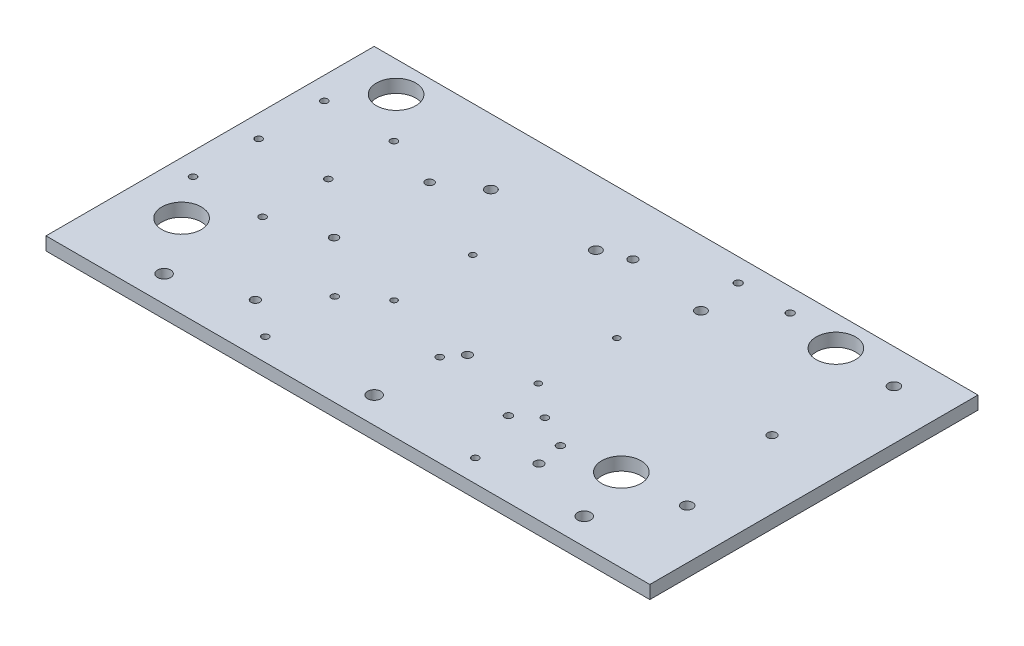
SolidWorks part; units mm, degrees
ref_plane "Front Plane" through (0, 0, 0) normal (0, 0, 1) x (1, 0, 0)
ref_plane "Top Plane" through (0, 0, 0) normal (0, 1, 0) x (1, 0, 0)
ref_plane "Right Plane" through (0, 0, 0) normal (1, 0, 0) x (0, 0, -1)
sketch "Sketch1" plane through (0, 0, 0) normal (0, 1, 0) x (1, 0, 0)
  line L1 (0, 0) -> (292.1, 0)
  line L2 (0, 0) -> (0, 158.75)
  line L3 (0, 158.75) -> (292.1, 158.75)
  line L4 (292.1, 0) -> (292.1, 158.75)
  dimension "D1" = 292.1
  dimension "D2" = 158.75
extrude "Boss-Extrude1" add sketch "Sketch1" along normal blind 6.35
sketch "Sketch2" plane through (0, 6.35, 0) normal (0, 1, 0) x (1, 0, 0)
  line L0 (0, 25.4) -> (292.1, 25.4) construction
  line L1 (0, 12.7) -> (292.1, 12.7) construction
  line L2 (146.05, 0) -> (146.05, 158.75) construction
  line L4 (0, 158.75) -> (0, 0)
  line L5 (0, 0) -> (292.1, 0)
  line L6 (292.1, 0) -> (292.1, 158.75)
  line L7 (292.1, 158.75) -> (0, 158.75)
  line L8 (0, 158.75) -> (0, 0) construction
  line L9 (0, 0) -> (292.1, 0) construction
  line L10 (292.1, 0) -> (292.1, 158.75) construction
  line L11 (292.1, 158.75) -> (0, 158.75) construction
  circle A0 centre (146.05, 12.7) radius 3.175
  circle A1 centre (247.65, 12.7) radius 3.175
  circle A2 centre (44.45, 12.7) radius 3.175
  dimension "D6" = 6.35
  dimension "D7" = 6.35
  dimension "D8" = 6.35
  dimension "D2" = 25.4
  dimension "D3" = 12.7
  dimension "D4" = 101.6
  dimension "D5" = 101.6
extrude "Cut-Extrude2" cut sketch "Sketch2" against normal blind 6.35
sketch "Sketch5" [suppressed] plane through (0, 6.35, 0) normal (0, 1, 0) x (1, 0, 0)
  line L0 (0, 0) -> (292.1, 0) construction
  line L1 (279.4, 31.75) -> (143.9, 31.75) construction
  line L2 (279.4, 31.75) -> (279.4, 75.25) construction
  line L3 (279.4, 75.25) -> (143.9, 75.25) construction
  line L4 (143.9, 31.75) -> (143.9, 75.25) construction
  line L5 (292.1, 0) -> (292.1, 158.75) construction
  circle A0 centre (279.4, 31.75) radius 1.525
  circle A1 centre (279.4, 75.25) radius 1.525
  circle A2 centre (143.9, 75.25) radius 1.525
  circle A3 centre (143.9, 31.75) radius 1.525
  dimension "D3" = 3.05
  dimension "D1" = 43.5
  dimension "D2" = 135.5
  dimension "D4" = 31.75
  dimension "D5" = 12.7
sketch "Sketch6" plane through (0, 6.35, 0) normal (0, 1, 0) x (1, 0, 0)
  line L0 (238.125, 158.75) -> (238.125, 0) construction
  line L1 (292.1, 158.75) -> (0, 158.75) construction
  line L2 (0, 0) -> (292.1, 0) construction
  line L4 (146.05, 158.75) -> (146.05, 0) construction
  line L5 (0, 25.4) -> (292.1, 25.4) construction
  line L6 (0, 158.75) -> (0, 0) construction
  line L7 (292.1, 0) -> (292.1, 158.75) construction
  line L8 (25.4, 40.1879) -> (238.125, 40.1879) construction
  line L9 (25.4, 143.9621) -> (238.125, 143.9621) construction
  line L10 (0, 92.075) -> (292.1, 92.075) construction
  line L11 (0, 158.75) -> (0, 25.4) construction
  line L12 (25.4, 143.9621) -> (25.4, 92.075) construction
  line L13 (25.4, 92.075) -> (25.4, 40.1879) construction
  circle A0 centre (25.4, 40.1879) radius 9.525
  circle A1 centre (238.125, 40.1879) radius 9.525
  circle A2 centre (25.4, 143.9621) radius 9.525
  circle A3 centre (238.125, 143.9621) radius 9.525
  dimension "D2" = 19.05
  dimension "D3" = 19.05
  dimension "D1" = 25.4
  dimension "D4" = 25.4
  dimension "D5" = 53.975
  dimension "D6" = 14.7879
extrude "Cut-Extrude3" cut sketch "Sketch6" against normal through all
sketch "Sketch8" plane through (0, 6.35, 0) normal (0, 1, 0) x (1, 0, 0)
  line L0 (265.43, 121.908) -> (265.43, 112.242) construction
  line L1 (270.764, 112.242) -> (270.764, 121.908) construction
  line L2 (265.43, 96.908) -> (265.43, 87.242)
  line L3 (270.764, 87.242) -> (270.764, 96.908)
  line L4 (265.43, 96.908) -> (265.43, 87.242) construction
  line L5 (270.764, 87.242) -> (270.764, 96.908) construction
  line L6 (265.43, 146.908) -> (265.43, 137.242) construction
  line L7 (270.764, 137.242) -> (270.764, 146.908) construction
  line L8 (265.43, 96.908) -> (265.43, 87.242) construction
  line L9 (270.764, 87.242) -> (270.764, 96.908) construction
  line L10 (265.43, 121.908) -> (265.43, 112.242) construction
  line L11 (270.764, 112.242) -> (270.764, 121.908) construction
  line L12 (265.43, 71.908) -> (265.43, 62.242) construction
  line L13 (270.764, 62.242) -> (270.764, 71.908) construction
  line L14 (265.43, 96.908) -> (265.43, 87.242) construction
  line L15 (270.764, 87.242) -> (270.764, 96.908) construction
  line L16 (265.43, 71.908) -> (265.43, 62.242) construction
  line L17 (270.764, 62.242) -> (270.764, 71.908) construction
  line L18 (265.43, 46.908) -> (265.43, 37.242) construction
  line L19 (270.764, 37.242) -> (270.764, 46.908) construction
  line L20 (265.43, 96.908) -> (265.43, 121.908) construction
  line L21 (268.097, 137.242) -> (268.097, 146.908) construction
  line L22 (268.097, 37.242) -> (268.097, 46.908) construction
  line L23 (143.764, 129.54) -> (134.239, 129.54) construction
  line L24 (134.239, 124.46) -> (143.764, 124.46) construction
  line L25 (213.1283, 38.3159) -> (211.5027, 38.3159)
  line L26 (211.5027, 34.7345) -> (213.1283, 34.7345)
  line L27 (222.285, 31.6611) -> (222.285, 152.4889)
  line L28 (222.285, 152.4889) -> (177.2, 152.4889)
  line L29 (177.2, 152.4889) -> (177.2, 31.6611)
  line L30 (177.2, 31.6611) -> (222.285, 31.6611)
  line L31 (222.285, 31.6611) -> (222.285, 152.4889) construction
  line L32 (222.285, 152.4889) -> (177.2, 152.4889) construction
  line L33 (177.2, 152.4889) -> (177.2, 31.6611) construction
  line L34 (177.2, 31.6611) -> (222.285, 31.6611) construction
  line L35 (213.1283, 38.3159) -> (211.5027, 38.3159) construction
  line L36 (211.5027, 34.7345) -> (213.1283, 34.7345) construction
  line L37 (187.9823, 38.3159) -> (186.3567, 38.3159)
  line L38 (186.3567, 34.7345) -> (187.9823, 34.7345)
  line L39 (187.9823, 38.3159) -> (186.3567, 38.3159) construction
  line L40 (186.3567, 34.7345) -> (187.9823, 34.7345) construction
  line L41 (211.5027, 145.8341) -> (213.1283, 145.8341)
  line L42 (213.1283, 149.4155) -> (211.5027, 149.4155)
  line L43 (211.5027, 145.8341) -> (213.1283, 145.8341) construction
  line L44 (213.1283, 149.4155) -> (211.5027, 149.4155) construction
  line L45 (186.3567, 145.8341) -> (187.9823, 145.8341)
  line L46 (187.9823, 149.4155) -> (186.3567, 149.4155)
  line L47 (186.3567, 145.8341) -> (187.9823, 145.8341) construction
  line L48 (187.9823, 149.4155) -> (186.3567, 149.4155) construction
  line L49 (194.564, 129.54) -> (185.039, 129.54)
  line L50 (185.039, 124.46) -> (194.564, 124.46)
  line L51 (194.564, 129.54) -> (185.039, 129.54) construction
  line L52 (185.039, 124.46) -> (194.564, 124.46) construction
  line L53 (92.964, 129.54) -> (83.439, 129.54) construction
  line L54 (83.439, 124.46) -> (92.964, 124.46) construction
  line L55 (194.564, 129.54) -> (143.764, 129.54) construction
  line L56 (83.439, 127) -> (194.564, 127) construction
  line L57 (189.8015, 124.46) -> (189.8015, 129.54) construction
  line L58 (88.2015, 124.46) -> (88.2015, 129.54) construction
  line L63 (109.05, 54.7) -> (183.05, 54.7)
  line L64 (183.05, 54.7) -> (183.05, 97.7)
  line L65 (183.05, 97.7) -> (109.05, 97.7)
  line L66 (109.05, 97.7) -> (109.05, 54.7)
  line L67 (109.05, 54.7) -> (183.05, 54.7) construction
  line L68 (183.05, 54.7) -> (183.05, 97.7) construction
  line L69 (183.05, 97.7) -> (109.05, 97.7) construction
  line L70 (109.05, 97.7) -> (109.05, 54.7) construction
  line L82 (186.3567, 36.5252) -> (187.9823, 36.5252) construction
  line L83 (211.5027, 36.5252) -> (213.1283, 36.5252) construction
  line L84 (211.5027, 147.6248) -> (213.1283, 147.6248) construction
  line L85 (186.3567, 147.6248) -> (187.9823, 147.6248) construction
  line L88 (70.3882, 66.9707) -> (81.4118, 66.9707)
  line L89 (81.4118, 70.9077) -> (70.3882, 70.9077)
  line L90 (70.3882, 66.9707) -> (81.4118, 66.9707) construction
  line L91 (81.4118, 70.9077) -> (70.3882, 70.9077) construction
  line L92 (77.8685, 63.0845) -> (77.8685, 68.9392)
  line L93 (73.9315, 68.9392) -> (73.9315, 63.0845)
  line L94 (126.4, 44.9707) -> (126.4, 139.1793)
  line L95 (25.4, 44.9707) -> (126.4, 44.9707)
  line L96 (25.4, 139.1793) -> (25.4, 44.9707)
  line L97 (126.4, 139.1793) -> (25.4, 139.1793)
  line L98 (126.4, 44.9707) -> (126.4, 139.1793) construction
  line L99 (25.4, 44.9707) -> (126.4, 44.9707) construction
  line L100 (25.4, 139.1793) -> (25.4, 44.9707) construction
  line L101 (126.4, 139.1793) -> (25.4, 139.1793) construction
  line L102 (77.8685, 63.0845) -> (77.8685, 68.9392) construction
  line L103 (73.9315, 68.9392) -> (73.9315, 63.0845) construction
  line L104 (73.9315, 115.2108) -> (73.9315, 109.3561)
  line L105 (77.8685, 109.3561) -> (77.8685, 115.2108)
  line L106 (73.9315, 115.2108) -> (73.9315, 109.3561) construction
  line L107 (77.8685, 109.3561) -> (77.8685, 115.2108) construction
  line L108 (70.3882, 113.2423) -> (81.4118, 113.2423)
  line L109 (81.4118, 117.1793) -> (70.3882, 117.1793)
  line L110 (70.3882, 113.2423) -> (81.4118, 113.2423) construction
  line L111 (81.4118, 117.1793) -> (70.3882, 117.1793) construction
  arc A0 (265.43, 112.242) -> (270.764, 112.242) centre (268.097, 112.242) ccw construction
  arc A1 (270.764, 121.908) -> (265.43, 121.908) centre (268.097, 121.908) ccw construction
  arc A2 (265.43, 87.242) -> (270.764, 87.242) centre (268.097, 87.242) ccw
  arc A3 (270.764, 96.908) -> (265.43, 96.908) centre (268.097, 96.908) ccw
  arc A4 (265.43, 87.242) -> (270.764, 87.242) centre (268.097, 87.242) ccw construction
  arc A5 (270.764, 96.908) -> (265.43, 96.908) centre (268.097, 96.908) ccw construction
  arc A6 (265.43, 137.242) -> (270.764, 137.242) centre (268.097, 137.242) ccw construction
  arc A7 (270.764, 146.908) -> (265.43, 146.908) centre (268.097, 146.908) ccw construction
  arc A8 (265.43, 87.242) -> (270.764, 87.242) centre (268.097, 87.242) ccw construction
  arc A9 (270.764, 96.908) -> (265.43, 96.908) centre (268.097, 96.908) ccw construction
  arc A10 (265.43, 112.242) -> (270.764, 112.242) centre (268.097, 112.242) ccw construction
  arc A11 (270.764, 121.908) -> (265.43, 121.908) centre (268.097, 121.908) ccw construction
  arc A12 (265.43, 62.242) -> (270.764, 62.242) centre (268.097, 62.242) ccw construction
  arc A13 (270.764, 71.908) -> (265.43, 71.908) centre (268.097, 71.908) ccw construction
  arc A14 (265.43, 87.242) -> (270.764, 87.242) centre (268.097, 87.242) ccw construction
  arc A15 (270.764, 96.908) -> (265.43, 96.908) centre (268.097, 96.908) ccw construction
  arc A16 (265.43, 62.242) -> (270.764, 62.242) centre (268.097, 62.242) ccw construction
  arc A17 (270.764, 71.908) -> (265.43, 71.908) centre (268.097, 71.908) ccw construction
  arc A18 (265.43, 37.242) -> (270.764, 37.242) centre (268.097, 37.242) ccw construction
  arc A19 (270.764, 46.908) -> (265.43, 46.908) centre (268.097, 46.908) ccw construction
  circle A20 centre (268.097, 42.075) radius 2.667
  circle A21 centre (268.097, 142.075) radius 2.667
  arc A22 (134.239, 129.54) -> (134.239, 124.46) centre (134.239, 127) ccw construction
  arc A23 (143.764, 124.46) -> (143.764, 129.54) centre (143.764, 127) ccw construction
  arc A24 (211.5027, 38.3159) -> (211.5027, 34.7345) centre (211.5027, 36.5252) ccw
  arc A25 (213.1283, 34.7345) -> (213.1283, 38.3159) centre (213.1283, 36.5252) ccw
  arc A26 (211.5027, 38.3159) -> (211.5027, 34.7345) centre (211.5027, 36.5252) ccw construction
  arc A27 (213.1283, 34.7345) -> (213.1283, 38.3159) centre (213.1283, 36.5252) ccw construction
  arc A28 (187.9823, 34.7345) -> (187.9823, 38.3159) centre (187.9823, 36.5252) ccw
  arc A29 (186.3567, 38.3159) -> (186.3567, 34.7345) centre (186.3567, 36.5252) ccw
  arc A30 (187.9823, 34.7345) -> (187.9823, 38.3159) centre (187.9823, 36.5252) ccw construction
  arc A31 (186.3567, 38.3159) -> (186.3567, 34.7345) centre (186.3567, 36.5252) ccw construction
  arc A32 (211.5027, 149.4155) -> (211.5027, 145.8341) centre (211.5027, 147.6248) ccw
  arc A33 (213.1283, 145.8341) -> (213.1283, 149.4155) centre (213.1283, 147.6248) ccw
  arc A34 (211.5027, 149.4155) -> (211.5027, 145.8341) centre (211.5027, 147.6248) ccw construction
  arc A35 (213.1283, 145.8341) -> (213.1283, 149.4155) centre (213.1283, 147.6248) ccw construction
  arc A36 (187.9823, 145.8341) -> (187.9823, 149.4155) centre (187.9823, 147.6248) ccw
  arc A37 (186.3567, 149.4155) -> (186.3567, 145.8341) centre (186.3567, 147.6248) ccw
  arc A38 (187.9823, 145.8341) -> (187.9823, 149.4155) centre (187.9823, 147.6248) ccw construction
  arc A39 (186.3567, 149.4155) -> (186.3567, 145.8341) centre (186.3567, 147.6248) ccw construction
  arc A40 (185.039, 129.54) -> (185.039, 124.46) centre (185.039, 127) ccw
  arc A41 (194.564, 124.46) -> (194.564, 129.54) centre (194.564, 127) ccw
  arc A42 (185.039, 129.54) -> (185.039, 124.46) centre (185.039, 127) ccw construction
  arc A43 (194.564, 124.46) -> (194.564, 129.54) centre (194.564, 127) ccw construction
  arc A44 (83.439, 129.54) -> (83.439, 124.46) centre (83.439, 127) ccw construction
  arc A45 (92.964, 124.46) -> (92.964, 129.54) centre (92.964, 127) ccw construction
  circle A46 centre (189.8015, 127) radius 2.54
  circle A47 centre (139.0015, 127) radius 2.54
  circle A48 centre (88.2015, 127) radius 2.54
  circle A50 centre (111.2, 57.2) radius 1.5
  circle A51 centre (111.2, 57.2) radius 1.5
  circle A52 centre (180.9, 57.2) radius 1.5
  circle A53 centre (180.9, 57.2) radius 1.5
  circle A54 centre (180.9, 95.2) radius 1.5
  circle A55 centre (180.9, 95.2) radius 1.5
  circle A56 centre (111.2, 95.2) radius 1.5
  circle A57 centre (111.2, 95.2) radius 1.5
  circle A58 centre (95.25, 10.795) radius 1.651
  circle A59 centre (95.25, 10.795) radius 1.651
  circle A60 centre (196.85, 10.795) radius 1.651
  circle A61 centre (196.85, 10.795) radius 1.651
  circle A62 centre (196.85, 44.45) radius 1.651
  circle A63 centre (196.85, 44.45) radius 1.651
  circle A64 centre (95.25, 44.45) radius 1.651
  circle A65 centre (95.25, 44.45) radius 1.651
  circle A66 centre (10.795, 123.825) radius 1.651
  circle A67 centre (10.795, 123.825) radius 1.651
  circle A68 centre (10.795, 60.325) radius 1.651
  circle A69 centre (10.795, 60.325) radius 1.651
  circle A70 centre (44.45, 60.325) radius 1.651
  circle A71 centre (44.45, 60.325) radius 1.651
  circle A72 centre (44.45, 123.825) radius 1.651
  circle A73 centre (44.45, 123.825) radius 1.651
  circle A74 centre (77.451, 23.8125) radius 2.0955
  circle A75 centre (77.451, 23.8125) radius 2.0955
  circle A77 centre (151.8, 132.099) radius 2.0955
  circle A78 centre (151.8, 132.099) radius 2.0955
  circle A80 centre (214.649, 23.8125) radius 2.0955
  circle A81 centre (214.649, 23.8125) radius 2.0955
  circle A83 centre (151.8, 52.051) radius 2.0955
  circle A84 centre (151.8, 52.051) radius 2.0955
  circle A86 centre (259.099, 92.075) radius 2.0955
  circle A87 centre (259.099, 92.075) radius 2.0955
  circle A88 centre (187.1695, 36.5252) radius 1.7907
  circle A89 centre (212.3155, 36.5252) radius 1.7907
  circle A90 centre (212.3155, 147.6248) radius 1.7907
  circle A91 centre (187.1695, 147.6248) radius 1.7907
  circle A92 centre (70.3882, 115.2108) radius 1.9685
  circle A93 centre (75.9, 68.9392) radius 3.3274
  circle A94 centre (75.9, 68.9392) radius 3.3274 construction
  circle A95 centre (75.9, 115.2108) radius 3.3274
  arc A96 (81.4118, 66.9707) -> (81.4118, 70.9077) centre (81.4118, 68.9392) ccw
  arc A97 (70.3882, 70.9077) -> (70.3882, 66.9707) centre (70.3882, 68.9392) ccw
  arc A98 (81.4118, 66.9707) -> (81.4118, 70.9077) centre (81.4118, 68.9392) ccw construction
  arc A99 (70.3882, 70.9077) -> (70.3882, 66.9707) centre (70.3882, 68.9392) ccw construction
  arc A100 (73.9315, 63.0845) -> (77.8685, 63.0845) centre (75.9, 63.0845) ccw
  arc A101 (77.8685, 68.9392) -> (73.9315, 68.9392) centre (75.9, 68.9392) ccw
  arc A102 (73.9315, 63.0845) -> (77.8685, 63.0845) centre (75.9, 63.0845) ccw construction
  arc A103 (77.8685, 68.9392) -> (73.9315, 68.9392) centre (75.9, 68.9392) ccw construction
  circle A104 centre (75.9, 115.2108) radius 3.3274 construction
  circle A105 centre (70.3882, 68.9392) radius 1.9685
  arc A106 (73.9315, 109.3561) -> (77.8685, 109.3561) centre (75.9, 109.3561) ccw
  arc A107 (77.8685, 115.2108) -> (73.9315, 115.2108) centre (75.9, 115.2108) ccw
  arc A108 (73.9315, 109.3561) -> (77.8685, 109.3561) centre (75.9, 109.3561) ccw construction
  arc A109 (77.8685, 115.2108) -> (73.9315, 115.2108) centre (75.9, 115.2108) ccw construction
  arc A110 (81.4118, 113.2423) -> (81.4118, 117.1793) centre (81.4118, 115.2108) ccw
  arc A111 (70.3882, 117.1793) -> (70.3882, 113.2423) centre (70.3882, 115.2108) ccw
  arc A112 (81.4118, 113.2423) -> (81.4118, 117.1793) centre (81.4118, 115.2108) ccw construction
  arc A113 (70.3882, 117.1793) -> (70.3882, 113.2423) centre (70.3882, 115.2108) ccw construction
  circle A121 centre (44.45, 92.075) radius 1.651 construction
  circle A122 centre (10.795, 92.075) radius 1.651 construction
  circle A123 centre (44.45, 92.075) radius 1.651
  circle A124 centre (10.795, 92.075) radius 1.651
  circle A129 centre (146.05, 44.45) radius 1.651 construction
  circle A130 centre (146.05, 44.45) radius 1.651
  dimension "D4" = 25
  dimension "D12" = 50.8
  dimension "D1" = 0
  dimension "D5" = 0
  dimension "D6" = 0
  dimension "D7" = 0
  dimension "D8" = 0
  dimension "D9" = 0
  dimension "D10" = 0
  dimension "D13" = 0
  dimension "D14" = 0
  dimension "D15" = 0
  dimension "D16" = 0
  dimension "D17" = 0
  dimension "D18" = 0
  dimension "D19" = 0
  dimension "D20" = 0
  dimension "D21" = 0
  dimension "D22" = 0
  dimension "D23" = 0
  dimension "D24" = 0
  dimension "D25" = 0
  dimension "D26" = 0
  dimension "D27" = 0
  dimension "D28" = 0
  dimension "D29" = 0
  dimension "D30" = 0
  dimension "D31" = 0
  dimension "D32" = 0
  dimension "D33" = 0
  dimension "D34" = 0
  dimension "D35" = 0
  dimension "D36" = 0
  dimension "D37" = 0
  dimension "D2" = 3
  dimension "D3" = 3
  dimension "D11" = 3
extrude "Cut-Extrude4" cut sketch "Sketch8" against normal through all
equation "\"D5@Sketch2\"=\"D4@Sketch2\""
equation "\"D7@Sketch2\"=\"D6@Sketch2\""
equation "\"D8@Sketch2\"=\"D7@Sketch2\""
equation "\"D4@Sketch5\"=1.25*25.4"
